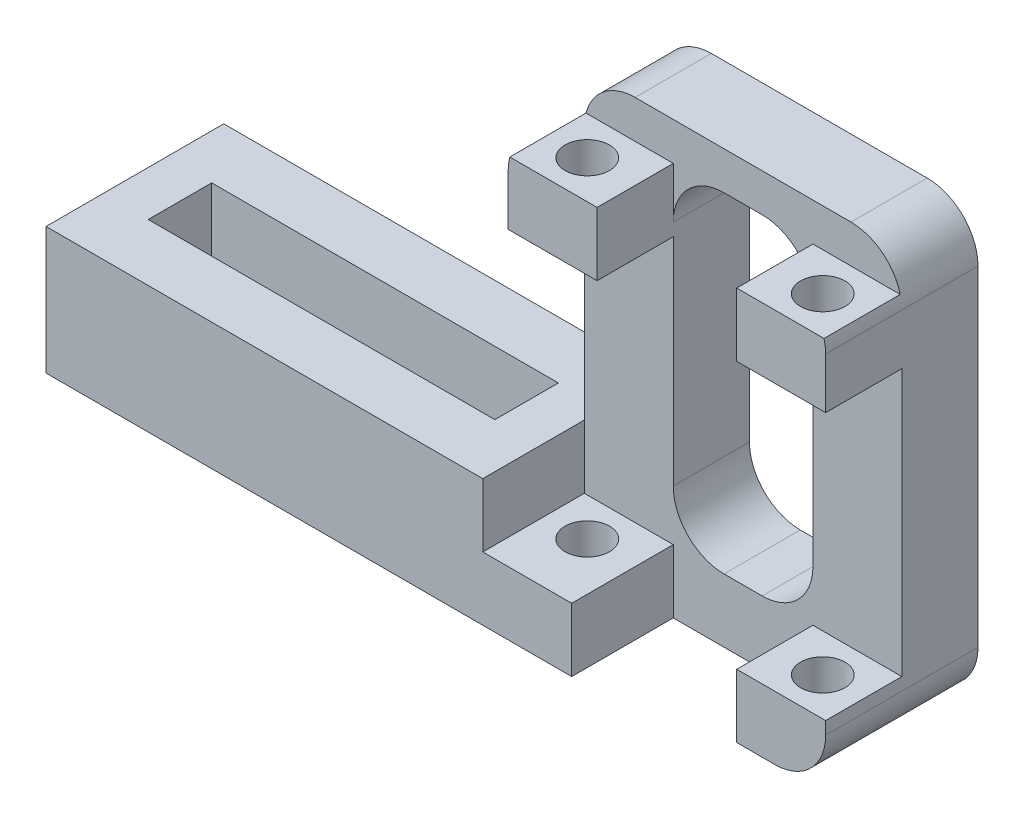
SolidWorks part; units mm, degrees
ref_plane "Alzado" through (0, 0, 0) normal (0, 0, 1) x (1, 0, 0)
ref_plane "Planta" through (0, 0, 0) normal (0, 1, 0) x (1, 0, 0)
ref_plane "Vista lateral" through (0, 0, 0) normal (1, 0, 0) x (0, 0, -1)
sketch "Croquis1" plane through (0, 0, 0) normal (0, 0, 1) x (1, 0, 0)
  line L1 (0, 0) -> (-25, 0)
  line L2 (0, 0) -> (0, -34)
  line L3 (0, -34) -> (-25, -34)
  line L4 (-25, 0) -> (-25, -34)
  dimension "D1" = 34
  dimension "D2" = 25
extrude "Saliente-Extruir1" add sketch "Croquis1" along normal blind 6
sketch "Croquis2" plane through (0, 0, 6) normal (0, 0, 1) x (1, 0, 0)
  line L0 (-25, 0) -> (-25, -34) construction
  line L1 (-25, -3) -> (-18, -3)
  line L2 (-25, -3) -> (-25, -8)
  line L3 (-25, -8) -> (-18, -8)
  line L4 (-18, -3) -> (-18, -8)
  line L5 (-12.5, 0) -> (-12.5, -3.7479) construction
  line L6 (0, 0) -> (-25, 0) construction
  line L7 (0, -8) -> (-7, -8)
  line L8 (-25, -34) -> (0, -34) construction
  line L9 (0, -34) -> (0, -29)
  line L10 (-7, -3) -> (-7, -8)
  line L11 (-18, 0) -> (-18, -3) construction
  line L12 (0, -3) -> (-7, -3)
  line L13 (0, -3) -> (0, -8)
  line L14 (-25, -29) -> (-18, -29)
  line L15 (-18, -34) -> (-18, -29)
  line L16 (-25, -34) -> (-18, -34)
  line L17 (-25, -34) -> (-25, -29)
  line L18 (0, -34) -> (-7, -34)
  line L19 (-7, -34) -> (-7, -29)
  line L20 (0, -29) -> (-7, -29)
  dimension "D1" = 5
  dimension "D2" = 3
  dimension "D3" = 7
  dimension "D4" = 7
  dimension "D5" = 5
extrude "Saliente-Extruir2" add sketch "Croquis2" along normal blind 6
sketch "Croquis3" plane through (0, 0, 6) normal (0, 0, 1) x (1, 0, 0)
  line L1 (-18, -3) -> (-7, -3)
  line L2 (-18, -3) -> (-18, -29)
  line L3 (-18, -29) -> (-7, -29)
  line L4 (-7, -3) -> (-7, -29)
extrude "Cortar-Extruir1" cut sketch "Croquis3" against normal up to next
fillet "Redondeo1" radius 4 8 edges at (-18, -29, 3) (-7, -29, 3) (-7, -3, 3) (-18, -3, 3) (0, 0, 3) (0, -34, 6) (-25, -34, 6) (-25, 0, 3)
sketch "Croquis5" plane through (0, 0, 0) normal (0, 0, -1) x (-1, 0, 0)
  line L0 (25, -29) -> (25, -30)
  line L1 (25, -34) -> (25, -36.4781) construction
  line L2 (25, -34) -> (59.4, -34)
  line L6 (25, -36.4781) -> (59.4, -36.4781) construction
  line L7 (25, -34) -> (21, -34)
  line L8 (25, -29) -> (25, -24)
  line L9 (25, -4) -> (25, -30) construction
  line L10 (25, -24) -> (59.4, -24)
  line L11 (59.4, -24) -> (59.4, -34)
  arc A1 (21, -34) -> (25, -30) centre (21, -30) ccw construction
  arc A2 (21, -34) -> (25, -30) centre (21, -30) ccw
  dimension "D1" = 34.4
  dimension "D2" = 10
extrude "Saliente-Extruir3" add sketch "Croquis5" against normal blind 12
sketch "Croquis6" plane through (0, 0, 12) normal (0, 0, 1) x (1, 0, 0)
  line L4 (-25, -29) -> (-25, -24)
  line L6 (-18, -29) -> (-25, -29)
  line L10 (-59.4, -34) -> (-18, -34)
  line L11 (-18, -34) -> (-18, -29)
  line L12 (-18, -29) -> (-25, -29)
  line L16 (-59.4, -34) -> (-18, -34)
  line L17 (-18, -34) -> (-18, -29)
  line L20 (-25, -29) -> (-25, -24)
  line L22 (-25, -24) -> (-59.4, -24)
  line L23 (-25, -24) -> (-59.4, -24)
  line L24 (-59.4, -24) -> (-59.4, -34)
  line L25 (-59.4, -24) -> (-59.4, -34)
  dimension "D1" = 0
extrude "Saliente-Extruir4" add sketch "Croquis6" along normal blind 2
sketch "Croquis7" plane through (0, -3, 0) normal (0, 1, 0) x (1, 0, 0)
  line L0 (-18, -12) -> (-18, -6) construction
  line L2 (-18, -6) -> (-7, -6) construction
  line L3 (-24.873, -6) -> (-24.873, -12) construction
  line L4 (-12.5, -8.2225) -> (-12.5, -6) construction
  circle A0 centre (-21.773, -9) radius 1.75
  circle A1 centre (-3.227, -9) radius 1.75
  point P4 (-18, -9)
  dimension "D1" = 3.5
  dimension "D2" = 3.1
extrude "Cortar-Extruir2" cut sketch "Croquis7" against normal up to surface (31 mm away) up to face at (-22.1, -34, 8)
sketch "Croquis8" plane through (0, -24, 0) normal (0, 1, 0) x (1, 0, 0)
  line L0 (-59.4, -14) -> (-59.4, 0) construction
  line L2 (-59.4, 0) -> (-25, 0) construction
  line L3 (-55.85, -8.1609) -> (-59.4, -8.1609) construction
  line L11 (-28.55, -4.5) -> (-55.85, -4.5)
  line L12 (-28.55, -4.5) -> (-28.55, -9.5)
  line L13 (-28.55, -9.5) -> (-55.85, -9.5)
  line L14 (-55.85, -4.5) -> (-55.85, -9.5)
  point P2 (-59.4, -7)
  point P3 (-55.85, -7)
  point P7 (-42.2, 0)
  point P8 (-42.2, -4.5)
  dimension "D1" = 5
  dimension "D2" = 27.3
extrude "Cortar-Extruir3" cut sketch "Croquis8" against normal up to next
